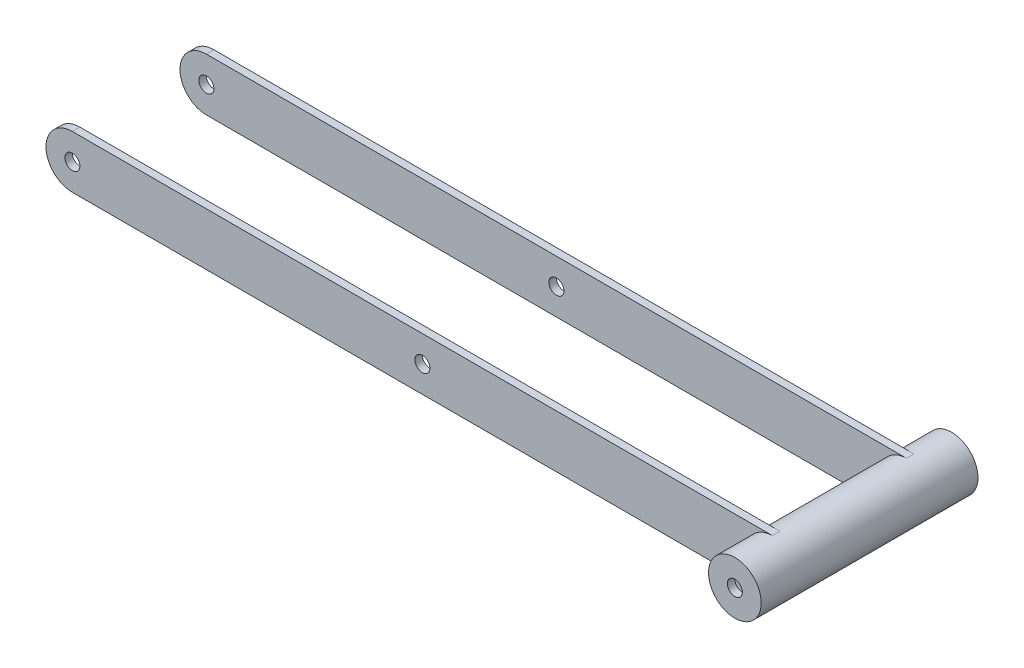
SolidWorks part; units mm, degrees
ref_plane "Front Plane" through (0, 0, 0) normal (0, 0, 1) x (1, 0, 0)
ref_plane "Top Plane" through (0, 0, 0) normal (0, 1, 0) x (1, 0, 0)
ref_plane "Right Plane" through (0, 0, 0) normal (1, 0, 0) x (0, 0, -1)
sketch "Sketch3" plane through (0, 0, 0) normal (0, 1, 0) x (1, 0, 0)
  line L1 (-250, 47) -> (250, 47)
  line L2 (-250, 47) -> (-250, -47)
  line L3 (-250, -47) -> (250, -47)
  line L4 (250, 47) -> (250, -47)
  line L5 (-250, 47) -> (250, -47) construction
  line L6 (-250, -47) -> (250, 47) construction
  point P0 (0, 0)
  dimension "D1" = 94
  dimension "D2" = 500
extrude "Boss-Extrude3" add sketch "Sketch3" along normal mid plane 35 contours L1 L4 L3 L2
sketch "Sketch4" plane through (0, 17.5, 0) normal (0, 1, 0) x (1, 0, 0)
  line L0 (-250, 47) -> (250, 47) construction
  line L1 (-250, 42) -> (250, 42)
  line L2 (-250, 42) -> (-250, -42)
  line L3 (-250, -42) -> (250, -42)
  line L4 (250, 42) -> (250, -42)
  line L5 (-250, 42) -> (250, -42) construction
  line L6 (-250, -42) -> (250, 42) construction
  point P0 (0, 0)
  dimension "D1" = 5
  dimension "D2" = 500
fillet "Fillet2" radius 17.5 4 edges at (250, -17.5, 0) (250, 17.5, 0) (-250, -17.5, 0) (-250, 17.5, 0)
extrude "Cut-Extrude2" cut sketch "Sketch4" against normal blind 35
sketch "Sketch9" plane through (0, 0, -47) normal (0, 0, -1) x (-1, 0, 0)
  line L0 (-250, 0) -> (250, 0) construction
  line L1 (232.5, 17.5) -> (232.5, -17.5) construction
  circle A0 centre (0, 0) radius 5
  circle A1 centre (232.5, 0) radius 5
  dimension "D1" = 10
  dimension "D2" = 10
extrude "Cut-Extrude4" cut sketch "Sketch9" against normal through all
sketch "Sketch5" plane through (0, 0, 0) normal (0, 0, 1) x (1, 0, 0)
  line L0 (232.5, 17.5) -> (232.5, -17.5) construction
  circle A0 centre (232.5, 0) radius 17.5
extrude "Boss-Extrude4" add sketch "Sketch5" along normal mid plane 144
sketch "Sketch8" plane through (0, 0, -72) normal (0, 0, -1) x (-1, 0, 0)
  line L0 (-250, 0) -> (-215, 0) construction
  circle A0 centre (-232.5, 0) radius 17.5 construction
  circle A1 centre (-232.5, 0) radius 5
  dimension "D1" = 10
extrude "Cut-Extrude3" cut sketch "Sketch8" against normal blind 5
mirror "Mirror1" about plane through (0, 0, 0) normal (0, 0, 1) of "Cut-Extrude3"
sketch "Sketch11" plane through (0, 0, 0) normal (1, 0, 0) x (0, 0, -1)
  line L0 (47, 0) -> (42, 0)
  dimension "D1" = 5
